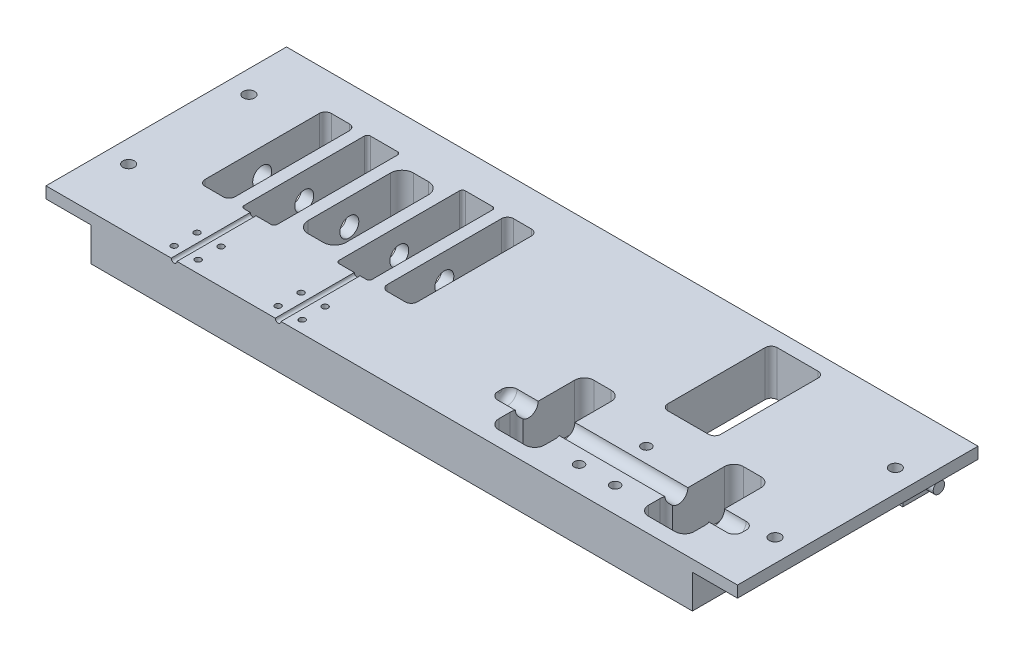
SolidWorks part; units mm, degrees
ref_plane "Front Plane" through (0, 0, 0) normal (0, 0, 1) x (1, 0, 0)
ref_plane "Top Plane" through (0, 0, 0) normal (0, 1, 0) x (1, 0, 0)
ref_plane "Right Plane" through (0, 0, 0) normal (1, 0, 0) x (0, 0, -1)
sketch "Sketch1" plane through (0, 0, 0) normal (0, 1, 0) x (1, 0, 0)
  line L1 (-115.841, 41.22) -> (176.259, 41.22)
  line L2 (-115.841, 41.22) -> (-115.841, -60.38)
  line L3 (-115.841, -60.38) -> (176.259, -60.38)
  line L4 (176.259, 41.22) -> (176.259, -60.38)
  dimension "D1" = 292.1
  dimension "D2" = 101.6
extrude "Boss-Extrude1" add sketch "Sketch1" along normal blind 25.4
sketch "Sketch3" plane through (0, 0, -41.22) normal (0, 0, -1) x (-1, 0, 0)
  line L0 (-176.259, 0) -> (-157.209, 0) construction
  line L1 (-176.259, 0) -> (115.841, 0) construction
  line L2 (-157.209, 0) -> (-157.209, 20.574) construction
  line L3 (-157.209, 20.574) -> (-176.259, 20.574)
  line L4 (-176.259, 25.4) -> (-176.259, 0) construction
  line L5 (-176.259, 20.574) -> (-176.259, 0)
  line L6 (-176.259, 0) -> (-157.209, 0)
  line L7 (-157.209, 0) -> (-157.209, 20.574)
  dimension "D1" = 19.05
  dimension "D2" = 20.574
extrude "Cut-Extrude1" cut sketch "Sketch3" against normal up to surface (101.6 mm away) up to face at (30.209, 12.7, 60.38)
sketch "Sketch4" plane through (157.209, 0, 0) normal (1, 0, 0) x (0, 0, -1)
  line L1 (-60.38, 0) -> (28.52, 0)
  line L2 (-60.38, 0) -> (-60.38, 6.35)
  line L3 (-60.38, 6.35) -> (28.52, 6.35)
  line L4 (28.52, 0) -> (28.52, 6.35)
  dimension "D1" = 88.9
  dimension "D2" = 6.35
extrude "Cut-Extrude2" cut sketch "Sketch4" against normal up to surface (273.05 mm away) up to face at (-115.841, 12.7, 9.58)
sketch "Sketch5" plane through (0, 0, -41.22) normal (0, 0, -1) x (-1, 0, 0)
  line L1 (115.841, 0) -> (96.791, 0)
  line L2 (115.841, 0) -> (115.841, 20.574)
  line L3 (115.841, 20.574) -> (96.791, 20.574)
  line L4 (96.791, 0) -> (96.791, 20.574)
  dimension "D1" = 20.574
  dimension "D2" = 19.05
sketch "Sketch8" plane through (0, 25.4, 0) normal (0, 1, 0) x (1, 0, 0)
  line L0 (176.259, 41.22) -> (-115.841, 41.22) construction
  line L1 (115.045, -11.358) -> (97.773, -11.358)
  line L2 (117.585, -8.818) -> (117.585, 32.33)
  line L3 (115.045, 34.87) -> (97.773, 34.87)
  line L4 (95.233, -8.818) -> (95.233, 32.33)
  line L5 (-36.593, -22.534) -> (-42.943, -22.534)
  line L6 (-31.767, -17.708) -> (-31.767, 17.09)
  line L7 (-36.593, 21.916) -> (-42.943, 21.916)
  line L8 (-47.769, -17.708) -> (-47.769, 17.09)
  line L11 (141.588, -15.789) -> (134.222, -15.789)
  line L13 (176.259, -60.38) -> (176.259, 41.22) construction
  line L15 (-115.841, -60.38) -> (176.259, -60.38) construction
  line L16 (130.158, -41.697) -> (130.158, -19.853)
  line L17 (143.493, -54.03) -> (132.317, -54.03)
  line L18 (147.557, -49.966) -> (147.557, -45.14)
  line L20 (128.253, -49.966) -> (128.253, -45.14)
  line L21 (145.652, -41.697) -> (145.652, -19.853)
  line L22 (78.342, -15.789) -> (70.976, -15.789)
  line L23 (66.912, -41.697) -> (66.912, -19.853)
  line L24 (80.247, -54.03) -> (69.071, -54.03)
  line L25 (84.311, -49.966) -> (84.311, -45.14)
  line L26 (65.007, -49.966) -> (65.007, -45.14)
  line L27 (82.406, -41.697) -> (82.406, -19.853)
  line L28 (-31.767, 9.6205) -> (95.233, 9.6205) construction
  arc A0 (117.585, 32.33) -> (115.045, 34.87) centre (115.045, 32.33) ccw
  arc A1 (95.233, 32.33) -> (97.773, 34.87) centre (97.773, 32.33) cw
  arc A2 (97.773, -11.358) -> (95.233, -8.818) centre (97.773, -8.818) cw
  arc A3 (115.045, -11.358) -> (117.585, -8.818) centre (115.045, -8.818) ccw
  arc A4 (-47.769, -17.708) -> (-42.943, -22.534) centre (-42.943, -17.708) ccw
  arc A5 (-47.769, 17.09) -> (-42.943, 21.916) centre (-42.943, 17.09) cw
  arc A6 (-31.767, 17.09) -> (-36.593, 21.916) centre (-36.593, 17.09) ccw
  arc A7 (-31.767, -17.708) -> (-36.593, -22.534) centre (-36.593, -17.708) cw
  arc A8 (128.253, -45.14) -> (130.158, -41.697) centre (132.317, -45.14) cw
  arc A9 (132.317, -54.03) -> (128.253, -49.966) centre (132.317, -49.966) cw
  arc A10 (147.557, -45.14) -> (145.652, -41.697) centre (143.493, -45.14) ccw
  arc A11 (147.557, -49.966) -> (143.493, -54.03) centre (143.493, -49.966) cw
  arc A12 (134.222, -15.789) -> (130.158, -19.853) centre (134.222, -19.853) ccw
  arc A13 (141.588, -15.789) -> (145.652, -19.853) centre (141.588, -19.853) cw
  arc A14 (65.007, -45.14) -> (66.912, -41.697) centre (69.071, -45.14) cw
  arc A15 (69.071, -54.03) -> (65.007, -49.966) centre (69.071, -49.966) cw
  arc A16 (84.311, -45.14) -> (82.406, -41.697) centre (80.247, -45.14) ccw
  arc A17 (84.311, -49.966) -> (80.247, -54.03) centre (80.247, -49.966) cw
  arc A18 (70.976, -15.789) -> (66.912, -19.853) centre (70.976, -19.853) ccw
  arc A19 (78.342, -15.789) -> (82.406, -19.853) centre (78.342, -19.853) cw
  point P22 (95.233, 34.87)
  point P25 (95.233, -11.358)
  point P28 (117.585, -11.358)
  point P31 (-47.769, -22.534)
  point P36 (-31.767, 21.916)
  point P39 (-31.767, -22.534)
  dimension "D9" = 2.54
  dimension "D10" = 4.826
  dimension "D17" = 4.826
  dimension "D11" = 4.064
  dimension "D14" = 4.064
  dimension "D23" = 4.064
  dimension "D24" = 4.064
  dimension "D26" = 11.176
  dimension "D1" = 46.228
  dimension "D2" = 6.35
  dimension "D3" = 58.674
  dimension "D4" = 22.352
  dimension "D5" = 19.304
  dimension "D6" = 127
  dimension "D7" = 16.002
  dimension "D8" = 44.45
  dimension "D12" = 30.607
  dimension "D13" = 6.35
  dimension "D15" = 11.176
  dimension "D16" = 7.366
  dimension "D18" = 21.844
  dimension "D19" = 6.35
  dimension "D20" = 93.853
  dimension "D21" = 7.366
  dimension "D22" = 21.844
  dimension "D25" = 4.826
extrude "Cut-Extrude4" cut sketch "Sketch8" against normal up to surface (25.4 mm away) up to face at (20.684, 0, -34.87)
sketch "Sketch10" plane through (0, 25.4, 0) normal (0, 1, 0) x (1, 0, 0)
  line L0 (-31.767, -17.708) -> (-31.767, 17.09) construction
  line L1 (-26.687, 26.361) -> (-12.717, 26.361)
  line L2 (-26.687, 26.361) -> (-26.687, -26.979)
  line L3 (-26.687, -26.979) -> (-12.717, -26.979)
  line L4 (-12.717, 26.361) -> (-12.717, -26.979)
  line L5 (-31.767, -0.309) -> (-26.687, -0.309) construction
  line L6 (-26.687, -0.309) -> (-12.717, -0.309) construction
  line L7 (-19.702, -26.979) -> (-19.702, 26.361) construction
  dimension "D1" = 5.08
  dimension "D2" = 13.97
  dimension "D3" = 53.34
extrude "Cut-Extrude5" cut sketch "Sketch10" against normal up to surface (19.05 mm away) up to face at (137.905, 6.35, 37.7048)
fillet "Fillet3" radius 1.27 1 edges at (-26.687, 15.875, -26.361)
fillet "Fillet4" radius 1.27 3 edges at (-26.687, 15.875, 26.979) (-12.717, 15.875, 26.979) (-12.717, 15.875, -26.361)
sketch "Sketch11" plane through (0, 25.4, 0) normal (0, 1, 0) x (1, 0, 0)
  line L0 (-12.717, -0.309) -> (-7.637, -0.309) construction
  line L1 (-7.637, 26.361) -> (5.063, 26.361)
  line L2 (-7.637, 26.361) -> (-7.637, -26.979)
  line L3 (-7.637, -26.979) -> (5.063, -26.979)
  line L4 (5.063, 26.361) -> (5.063, -26.979)
  line L5 (-12.717, -25.709) -> (-12.717, 25.091) construction
  line L6 (5.063, -0.309) -> (-7.637, -0.309) construction
  line L7 (-1.287, 26.361) -> (-1.287, -26.979) construction
  dimension "D1" = 5.08
  dimension "D2" = 12.7
  dimension "D3" = 53.34
extrude "Cut-Extrude6" cut sketch "Sketch11" against normal up to surface (19.05 mm away) up to face at (-19.702, 6.35, 0.309)
fillet "Fillet5" radius 2.54 4 edges at (-7.637, 15.875, 26.979) (5.063, 15.875, 26.979) (5.063, 15.875, -26.361) (-7.637, 15.875, -26.361)
sketch "Sketch12" plane through (0, 25.4, 0) normal (0, 1, 0) x (1, 0, 0)
  line L0 (-59.834, 26.361) -> (-59.834, -26.979) construction
  line L1 (-66.819, 26.361) -> (-52.849, 26.361)
  line L2 (-66.819, 26.361) -> (-66.819, -26.979)
  line L3 (-66.819, -26.979) -> (-52.849, -26.979)
  line L4 (-52.849, 26.361) -> (-52.849, -26.979)
  line L5 (-66.819, -0.309) -> (-52.849, -0.309) construction
  line L6 (-52.849, -0.309) -> (-47.769, -0.309) construction
  line L7 (-47.769, 17.09) -> (-47.769, -17.708) construction
  dimension "D1" = 53.34
  dimension "D2" = 13.97
  dimension "D3" = 5.08
extrude "Cut-Extrude7" cut sketch "Sketch12" against normal up to surface (19.05 mm away) up to face at (-1.287, 6.35, 0.309)
sketch "Sketch14" plane through (0, 25.4, 0) normal (0, 1, 0) x (1, 0, 0)
  line L0 (-78.249, 26.361) -> (-78.249, -26.979) construction
  line L1 (-84.599, 26.361) -> (-71.899, 26.361)
  line L2 (-84.599, 26.361) -> (-84.599, -26.979)
  line L3 (-84.599, -26.979) -> (-71.899, -26.979)
  line L4 (-71.899, 26.361) -> (-71.899, -26.979)
  line L5 (-84.599, -0.309) -> (-71.899, -0.309) construction
  line L6 (-71.899, -0.309) -> (-66.819, -0.309) construction
  line L7 (-66.819, 26.361) -> (-66.819, -26.979) construction
  line L10 (-71.899, -0.309) -> (-66.819, -0.309) construction
  dimension "D1" = 53.34
  dimension "D2" = 12.7
  dimension "D3" = 5.08
extrude "Cut-Extrude9" cut sketch "Sketch14" against normal up to surface (19.05 mm away) up to face at (-59.834, 6.35, 0.309)
fillet "Fillet8" radius 2.54 4 edges at (-71.899, 15.875, 26.979) (-84.599, 15.875, 26.979) (-71.899, 15.875, -26.361) (-84.599, 15.875, -26.361)
fillet "Fillet9" radius 1.27 4 edges at (-52.849, 15.875, 26.979) (-66.819, 15.875, 26.979) (-52.849, 15.875, -26.361) (-66.819, 15.875, -26.361)
extrude "Cut-Extrude10" cut sketch "Sketch5" against normal up to surface (101.6 mm away) contours L3 L4 L1 L2 up to face at (72.5423, 17.4413, 60.38)
sketch "Sketch21" plane through (-84.599, 0, 0) normal (1, 0, 0) x (0, 0, -1)
  line L0 (-0.309, 18.3642) -> (-0.309, 25.4) construction
  line L1 (23.821, 25.4) -> (-24.439, 25.4) construction
  circle A0 centre (-0.309, 14.3642) radius 4
  dimension "D1" = 8
  dimension "D2" = 7.0358
extrude "Cut-Extrude11" cut sketch "Sketch21" against normal up to surface (12.192 mm away) contours A0 up to face at (-96.791, 8.9747, -3.12)
sketch "Sketch25" plane through (-96.791, 0, 0) normal (-1, 0, 0) x (0, 0, 1)
  line L0 (0.309, 18.3642) -> (0.309, 25.4) construction
  line L1 (-41.22, 25.4) -> (60.38, 25.4) construction
  line L2 (0.309, 10.3642) -> (0.309, 6.35) construction
  line L3 (-28.52, 6.35) -> (60.38, 6.35) construction
  circle A0 centre (0.309, 14.3642) radius 4
  dimension "D2" = 8
  dimension "D1" = 7.0358
  dimension "D3" = 4.0142
extrude "Cut-Extrude14" cut sketch "Sketch25" along direction (-1, 0, 0) on the side against the normal up to surface (101.854 mm away) up to face at (5.063, 15.875, 0.309)
sketch "Sketch27" plane through (0, 0, 26.979) normal (0, 0, -1) x (-1, 0, 0)
  line L0 (65.549, 25.4) -> (54.119, 25.4) construction
  line L1 (61.739, 25.4) -> (54.119, 25.4) construction
  circle A0 centre (61.739, 25.4) radius 1.2065
  dimension "D1" = 7.62
  dimension "D3" = 2.413
extrude "Cut-Extrude15" cut sketch "Sketch27" along direction (0, 0, 1) on the side against the normal up to surface (33.401 mm away) up to face at (30.209, 18.2245, 60.38)
sketch "Sketch28" plane through (0, 0, 26.979) normal (0, 0, -1) x (-1, 0, 0)
  line L0 (25.417, 25.4) -> (13.987, 25.4) construction
  line L1 (17.797, 25.4) -> (25.417, 25.4) construction
  circle A1 centre (17.797, 25.4) radius 1.2065
  dimension "D1" = 7.62
  dimension "D2" = 2.413
extrude "Cut-Extrude16" cut sketch "Sketch28" along direction (0, 0, 1) on the side against the normal up to surface (33.401 mm away) up to face at (11.8194, 19.539, 60.38)
sketch "Sketch30" plane through (0, 25.4, 0) normal (0, 1, 0) x (1, 0, 0)
  line L0 (176.259, -60.38) -> (176.259, 41.22) construction
  line L1 (157.971, -39.298) -> (54.847, -39.298)
  line L2 (157.971, -39.298) -> (157.971, -35.234)
  line L3 (157.971, -35.234) -> (54.847, -35.234)
  line L4 (54.847, -39.298) -> (54.847, -35.234)
  line L5 (-16.5905, -60.38) -> (176.259, -60.38) construction
  dimension "D1" = 18.288
  dimension "D2" = 4.064
  dimension "D3" = 103.124
  dimension "D4" = 25.146
revolve "Cut-Revolve1" cut sketch "Sketch30" angle 360 about L1
fillet "Fillet17" radius 3.175 1 edges at (157.971, 21.336, 39.298) type face fillet first side face at (150.9491, 23.4215, 39.613) second side face at (157.971, 23.368, 39.298)
fillet "Fillet18" radius 3.175 1 edges at (54.847, 21.336, 39.298) type face fillet first side face at (61.6989, 23.462, 39.6375) second side face at (54.847, 23.368, 39.298)
sketch "Sketch32" plane through (0, 25.4, 0) normal (0, 1, 0) x (1, 0, 0)
  line L0 (106.282, -43.362) -> (106.282, -56.062) construction
  line L1 (83.9014, -43.362) -> (128.6626, -43.362) construction
  line L2 (106.282, -49.712) -> (113.902, -49.712) construction
  line L3 (106.282, -35.234) -> (106.282, -22.534) construction
  line L4 (130.158, -35.234) -> (82.406, -35.234) construction
  line L5 (106.282, -49.712) -> (98.662, -49.712) construction
  circle A0 centre (106.282, -28.884) radius 2.032
  circle A1 centre (98.662, -49.712) radius 2.032
  circle A2 centre (113.902, -49.712) radius 2.032
  dimension "D3" = 4.064
  dimension "D5" = 4.064
  dimension "D7" = 4.064
  dimension "D1" = 12.7
  dimension "D2" = 12.7
  dimension "D4" = 7.62
  dimension "D6" = 7.62
extrude "Cut-Extrude19" cut sketch "Sketch32" against normal up to surface (19.05 mm away) up to face at (-39.768, 6.35, 0.309)
sketch "Sketch33" plane through (-96.791, 0, 0) normal (-1, 0, 0) x (0, 0, 1)
  line L1 (-28.52, 6.35) -> (-41.22, 6.35)
  line L2 (-28.52, 6.35) -> (-28.52, 0)
  line L3 (-28.52, 0) -> (-41.22, 0)
  line L4 (-41.22, 6.35) -> (-41.22, 0)
extrude "Cut-Extrude20" cut sketch "Sketch33" against normal up to surface (254 mm away) up to face at (157.209, 8.9747, -3.12)
sketch "Sketch34" plane through (95.233, 0, 0) normal (1, 0, 0) x (0, 0, -1)
  line L0 (11.756, 15.875) -> (11.756, 25.4) construction
  line L1 (32.33, 25.4) -> (-8.818, 25.4) construction
  line L2 (-8.818, 15.875) -> (11.756, 15.875) construction
  line L3 (-8.818, 6.35) -> (-8.818, 25.4) construction
  circle A0 centre (11.756, 15.875) radius 4
  dimension "D1" = 8
sketch "Sketch36" plane through (0, 25.4, 0) normal (0, 1, 0) x (1, 0, 0)
  line L0 (117.585, 11.756) -> (122.665, 11.756) construction
  line L1 (122.665, -6.024) -> (137.905, -6.024)
  line L2 (122.665, -6.024) -> (122.665, 29.536)
  line L3 (122.665, 29.536) -> (137.905, 29.536)
  line L4 (137.905, -6.024) -> (137.905, 29.536)
  line L5 (117.585, -8.818) -> (117.585, 32.33) construction
  line L6 (130.285, -6.024) -> (130.285, 29.536) construction
  line L7 (137.905, 11.756) -> (122.665, 11.756) construction
  dimension "D1" = 5.08
  dimension "D2" = 35.56
  dimension "D3" = 15.24
extrude "Cut-Extrude22" cut sketch "Sketch34" along normal up to surface (61.976 mm away) up to face at (157.209, 13.462, 9.58)
ref_plane "Plane1" through (30.209, 0, 0) normal (1, 0, 0) x (0, 0, -1)
sketch "Sketch38" plane through (0, 20.574, 0) normal (0, -1, 0) x (1, 0, 0)
  line L0 (176.259, 34.98) -> (157.209, 34.98) construction
  line L1 (176.259, 60.38) -> (176.259, -41.22) construction
  line L2 (157.209, -41.22) -> (157.209, 60.38) construction
  line L3 (166.734, 34.98) -> (166.734, -15.82) construction
  line L5 (176.259, -15.82) -> (157.209, -15.82) construction
  line L6 (176.259, 9.58) -> (157.209, 9.58) construction
  line L8 (157.209, 60.38) -> (157.209, -41.22) construction
  circle A0 centre (166.734, 34.98) radius 2.413
  circle A1 centre (166.734, -15.82) radius 2.413
  point P15 (166.734, 9.58)
  dimension "D1" = 4.826
  dimension "D2" = 4.826
  dimension "D3" = 50.8
extrude "Cut-Extrude23" cut sketch "Sketch38" against normal up to surface (4.826 mm away) up to face at (106.282, 25.4, 30.916)
mirror "Mirror1" about plane through (30.209, 0, 0) normal (1, 0, 0) of "Cut-Extrude23"
sketch "Sketch40" plane through (0, 25.4, 0) normal (0, 1, 0) x (1, 0, 0)
  line L0 (-66.819, -55.3) -> (-66.819, -60.38) construction
  line L1 (-115.841, -60.38) -> (-62.9455, -60.38) construction
  line L2 (-66.819, -55.3) -> (-62.9455, -55.3) construction
  line L3 (-62.9455, -26.979) -> (-62.9455, -60.38) construction
  line L4 (-66.819, -45.6127) -> (-66.819, -55.3) construction
  line L5 (-56.659, -55.3) -> (-66.819, -55.3) construction
  line L6 (-66.819, -45.6127) -> (-56.659, -45.6127) construction
  line L7 (-56.659, -45.6127) -> (-56.659, -55.3) construction
  line L8 (-56.659, -50.4564) -> (-60.5325, -50.4564) construction
  line L9 (-60.5325, -60.38) -> (-60.5325, -26.979) construction
  circle A0 centre (-66.819, -55.3) radius 1.27
  circle A1 centre (-66.819, -45.6127) radius 1.27
  circle A2 centre (-56.659, -55.3) radius 1.27
  circle A3 centre (-56.659, -45.6127) radius 1.27
  dimension "D1" = 2.54
  dimension "D4" = 2.54
  dimension "D6" = 2.54
  dimension "D9" = 2.54
  dimension "D2" = 5.08
  dimension "D3" = 3.8735
  dimension "D5" = 9.6873
  dimension "D7" = 10.16
  dimension "D8" = 3.8735
extrude "Cut-Extrude24" cut sketch "Sketch40" against normal blind 2.54
ref_axis "Axis1" through (-39.768, 25.4, 22.534) along (0, 0, 1)
ref_plane "Plane2" through (-39.768, 0, 0) normal (-1, 0, 0) x (0, 0, 1)
mirror "Mirror2" about plane through (-39.768, 0, 0) normal (-1, 0, 0) of "Cut-Extrude24"
sketch "Sketch42" plane through (0, 6.35, 0) normal (0, -1, 0) x (1, 0, 0)
  line L1 (-96.791, -41.22) -> (-87.901, -41.22)
  line L2 (-96.791, -41.22) -> (-96.791, -28.52)
  line L3 (-96.791, -28.52) -> (-87.901, -28.52)
  line L4 (-87.901, -41.22) -> (-87.901, -28.52)
  dimension "D1" = 12.7
  dimension "D2" = 8.89
extrude "Boss-Extrude2" add sketch "Sketch42" along normal blind 6.35
sketch "Sketch43" plane through (-96.791, 0, 0) normal (-1, 0, 0) x (0, 0, 1)
  line L0 (-36.14, 0) -> (-36.14, 7.112) construction
  line L1 (-28.52, 0) -> (-41.22, 0) construction
  line L2 (-36.14, 7.112) -> (-41.22, 7.112) construction
  line L3 (-41.22, 0) -> (-41.22, 20.574) construction
  circle A0 centre (-36.14, 7.112) radius 2.413
  dimension "D3" = 4.826
  dimension "D1" = 5.08
  dimension "D2" = 7.112
extrude "Boss-Extrude3" add sketch "Sketch43" along normal blind 7.62
mirror "Mirror3" about plane through (30.209, 0, 0) normal (1, 0, 0) of "Boss-Extrude3", "Boss-Extrude2"
